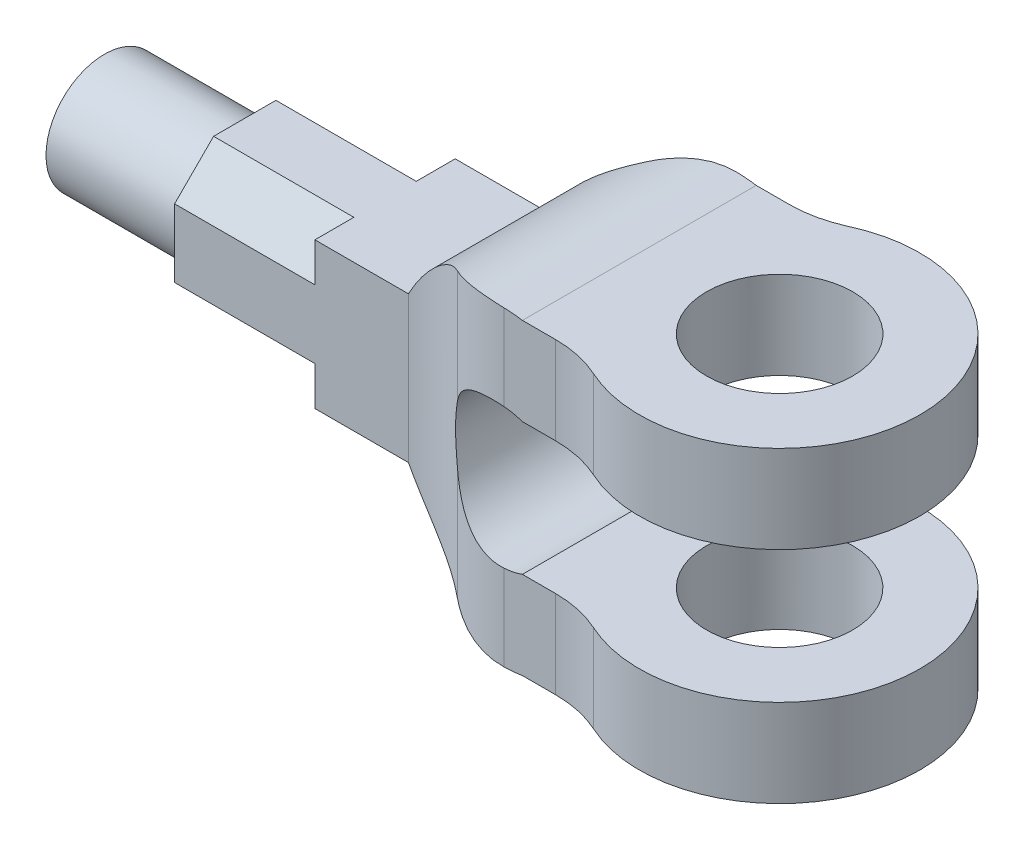
SolidWorks part; units mm, degrees
ref_plane "Front Plane" through (0, 0, 0) normal (0, 0, 1) x (1, 0, 0)
ref_plane "Top Plane" through (0, 0, 0) normal (0, 1, 0) x (1, 0, 0)
ref_plane "Right Plane" through (0, 0, 0) normal (1, 0, 0) x (0, 0, -1)
sketch "Sketch4" plane through (0, 0, 0) normal (0, 1, 0) x (1, 0, 0)
  circle A0 centre (0, 0) radius 6.25
  circle A1 centre (0, 0) radius 12
  dimension "D1" = 12.5
  dimension "D2" = 24
extrude "Boss-Extrude2" add sketch "Sketch4" along normal blind 7.5
sketch "Sketch5" plane through (0, 0, 0) normal (0, 0, 1) x (1, 0, 0)
  line L0 (-20, -5.6569) -> (-52.6483, -5.6569) construction
  line L1 (-20, -5.6569) -> (13.9554, -5.6569) construction
  line L2 (-25.7491, 0.5931) -> (-45.7491, 0.5931)
  line L3 (-12, 7.5) -> (12, 7.5)
  line L4 (12, 7.5) -> (12, 0)
  line L5 (12, 0) -> (-12, 0)
  line L6 (-45.7491, 0.5931) -> (-45.7491, -5.6569)
  line L7 (-45.7491, -5.6569) -> (-20, -5.6569)
  arc A2 (-12, 0) -> (-20, -5.6569) centre (-14, -5.6569) ccw
  arc A4 (-12, 7.5) -> (-25.7491, 0.5931) centre (-14, -5.6569) ccw
  point P6 (-12, -5.6569)
  dimension "D1" = 12
  dimension "D2" = 8
  dimension "D3" = 20
  dimension "D4" = 12.5
extrude "Boss-Extrude3" add sketch "Sketch5" along normal mid plane 20
sketch "Sketch6" plane through (0, 0, 0) normal (0, -1, 0) x (1, 0, 0)
  line L4 (12, -10) -> (12, 10)
  line L5 (12, 10) -> (6.6332, 10)
  line L6 (-12, 10) -> (-12, -10)
  line L7 (-12, -10) -> (-6.6332, -10)
  line L8 (12, -10) -> (12, 10)
  line L9 (12, 10) -> (6.6332, 10)
  line L10 (-12, 10) -> (-12, -10)
  line L11 (-12, -10) -> (-6.6332, -10)
  line L14 (-6.6332, 10) -> (-12, 10)
  line L15 (-6.6332, 10) -> (-12, 10)
  line L16 (6.6332, -10) -> (12, -10)
  line L17 (6.6332, -10) -> (12, -10)
  circle A0 centre (0, 0) radius 6.25 construction
  circle A1 centre (0, 0) radius 6.25
  circle A2 centre (0, 0) radius 12 construction
  circle A3 centre (0, 0) radius 12
  arc A6 (6.6332, 10) -> (-6.6332, 10) centre (0, 0) ccw
  arc A7 (6.6332, 10) -> (-6.6332, 10) centre (0, 0) ccw
  arc A8 (-6.6332, -10) -> (6.6332, -10) centre (0, 0) ccw
  arc A9 (-6.6332, -10) -> (6.6332, -10) centre (0, 0) ccw
  line M5 (12, -10) -> (12, 10)
  line M6 (12, 10) -> (6.6332, 10)
  line M7 (-12, 10) -> (-12, -10)
  line M8 (-12, -10) -> (-6.6332, -10)
  dimension "D1" = 0
extrude "Cut-Extrude1" cut sketch "Sketch6" against normal blind 20 contours A3 L11 M5 | A3 L8 M6 | A3 L9 M7 | A3 L10 M8 | A1 region at (10.4784, 0, -7.6254) region at (10.4784, 0, 7.6254) region at (-10.4784, 0, -7.6254) region at (-10.4784, 0, 7.6254) region at (0, 0, 0)
sketch "Sketch7" plane through (-12, 0, 0) normal (1, 0, 0) x (0, 0, -1)
  line L4 (10, 7.5) -> (-10, 7.5)
  line L5 (-10, 7.5) -> (-10, 0)
  line L6 (-10, 0) -> (10, 0)
  line L7 (10, 0) -> (10, 7.5)
  line L8 (10, 7.5) -> (-10, 7.5)
  line L9 (-10, 7.5) -> (-10, 0)
  line L10 (-10, 0) -> (10, 0)
  line L11 (10, 0) -> (10, 7.5)
  dimension "D1" = 0
extrude "Boss-Extrude4" add sketch "Sketch7" along normal up to surface (5.3668 mm away) up to face at (0, 0, -12)
mirror "Mirror2" about plane through (-45.7491, -5.6569, 10) normal (0, 1, 0) of bodies 106
ref_plane "Plane1" through (0, -5.6569, 0) normal (0, -1, 0) x (-1, 0, 0)
sketch "Sketch8" plane through (0, -5.6569, 0) normal (0, -1, 0) x (-1, 0, 0)
  line L0 (25.7491, -10) -> (25.7491, 10) construction
  line L1 (-14.6388, 0) -> (14.6388, 0) construction
  line L2 (25.7491, 6) -> (45.7491, 6)
  line L3 (45.7491, -10) -> (45.7491, 10) construction
  line L4 (25.7491, -6) -> (45.7491, -6)
  line L5 (45.7491, -6) -> (45.7491, 6)
  line L7 (17.5073, 10) -> (45.7491, 10)
  line L8 (25.7491, 10) -> (12, 10) construction
  line L10 (17.5073, -10) -> (45.7491, -10)
  line L11 (45.7491, 10) -> (45.7491, 6)
  line L13 (45.7491, -10) -> (45.7491, -6)
  arc A3 (25.7491, 6) -> (17.5073, 10) centre (25.7491, 16.4907) cw
  arc A4 (25.7491, -6) -> (17.5073, -10) centre (25.7491, -16.4907) ccw
  point P8 (13.15, 10)
  point P16 (0, 0)
  point P20 (18, 10)
  point P21 (18, 10)
  point P22 (14.6078, 10)
  point P27 (17.5073, 10)
  dimension "D1" = 12
extrude "Cut-Extrude2" cut sketch "Sketch8" against normal through all both and the other way through all contours L2 L11 | L13 L4 region at (-32.8061, -5.6569, -8.0827) region at (-32.8061, -5.6569, 8.0827)
fillet "Fillet1" radius 10 2 edges at (-17.5073, -14.5097, -10) (-17.5073, 3.196, -10)
fillet "Fillet2" radius 10 1 edges at (-17.5073, -14.5097, 10)
sketch "Sketch9" plane through (-45.7491, 0, 0) normal (-1, 0, 0) x (0, 0, 1)
  line L0 (-6, -2.7402) -> (-2.6667, 0.5931)
  line L1 (-6, 0.5931) -> (-6, -11.9069) construction
  line L2 (6, 0.5931) -> (-6, 0.5931) construction
  line L3 (-6, -2.7402) -> (-6, 0.5931)
  line L4 (-6, 0.5931) -> (-2.6667, 0.5931)
  line L5 (0, -14.6388) -> (0, 14.6388) construction
  line L6 (6, 0.5931) -> (2.6667, 0.5931)
  line L7 (6, -2.7402) -> (2.6667, 0.5931)
  line L8 (6, -2.7402) -> (6, 0.5931)
  line L9 (-6, -5.6569) -> (6, -5.6569) construction
  line L10 (6, 0.5931) -> (6, -11.9069) construction
  line L11 (6, -8.5735) -> (6, -11.9069)
  line L12 (6, -8.5735) -> (2.6667, -11.9069)
  line L13 (6, -11.9069) -> (2.6667, -11.9069)
  line L14 (-6, -8.5735) -> (-6, -11.9069)
  line L15 (-6, -8.5735) -> (-2.6667, -11.9069)
  line L16 (-6, -11.9069) -> (-2.6667, -11.9069)
  dimension "D1" = 3.3333
  dimension "D2" = 3.3333
extrude "Cut-Extrude3" cut sketch "Sketch9" against normal blind 12
sketch "Sketch10" plane through (-45.7491, 0, 0) normal (-1, 0, 0) x (0, 0, 1)
  line L0 (-6, -2.7402) -> (-6, -8.5735) construction
  circle A0 centre (0, -5.6569) radius 5
  point P2 (0, 0)
  point P4 (0, 0)
  point P5 (0, -5.1245)
  point P6 (0, 0)
  point P9 (-6, -5.6569)
  dimension "D1" = 10
extrude "Boss-Extrude5" add sketch "Sketch10" along normal blind 12
fillet "Fillet3" radius 10 4 edges at (-6.6332, -15.0637, 10) (-6.6332, 3.75, -10) (-6.6332, -15.0637, -10) (-6.6332, 3.75, 10)
equation "\"d\"= 10"
equation "\"d1\"= \"d\""
equation "\"d2\"= 2 * \"d\""
equation "\"d3\"= 1.5 * \"d\""
equation "\"t\"= 1.25 * \"d\""
equation "\"t1\"= 0.75 * \"d\""
equation "\"t2\"= 0.5 * \"d\""
equation "\"D2@Sketch4\"=\"d1\"*2.4"
equation "\"D1@Sketch4\"=\"d\"*1.25"
equation "\"D1@Boss-Extrude2\"=\"t1\""
equation "\"D1@Sketch5\"=\"d\"*1.2"
equation "\"D3@Sketch5\"=\"d\"*2"
equation "\"D4@Sketch5\"=\"d\"*1.25"
equation "\"D1@Boss-Extrude3\"=2*\"d\""
equation "\"D1@Sketch9\"=\"d\"/3"
equation "\"D2@Sketch9\"=\"d\"/3"
equation "\"D1@Cut-Extrude3\"=1.2*\"d\""
equation "\"D1@Sketch10\"=\"d\""
equation "\"D1@Boss-Extrude5\"=1.2*\"d\""
